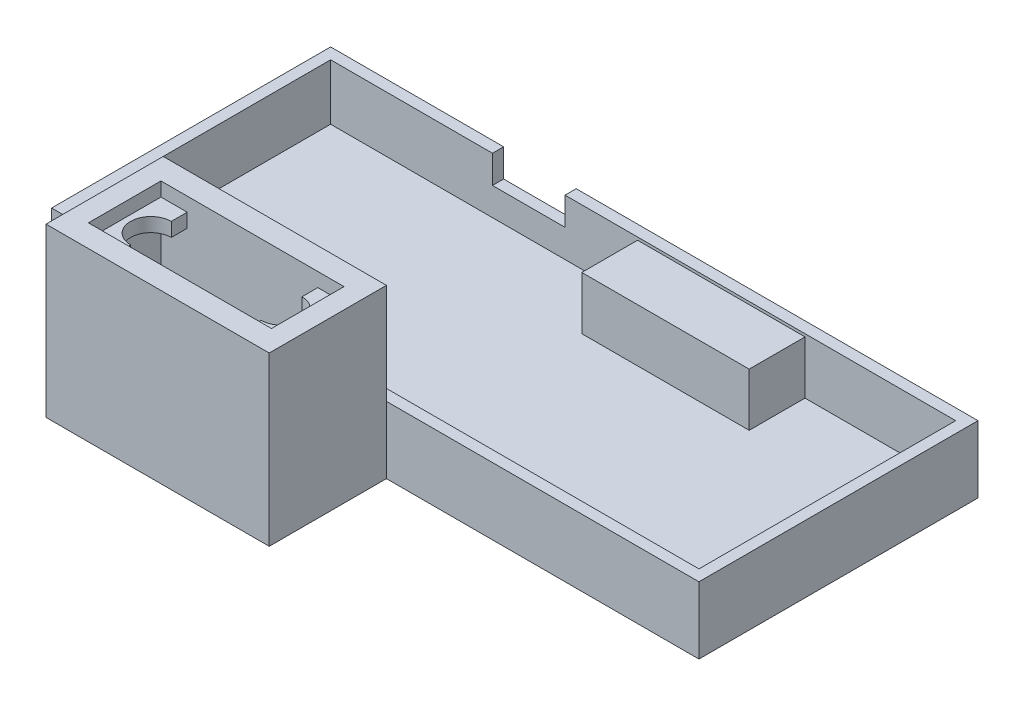
SolidWorks part; units mm, degrees
ref_plane "Front Plane" through (0, 0, 0) normal (0, 0, 1) x (1, 0, 0)
ref_plane "Top Plane" through (0, 0, 0) normal (0, 1, 0) x (1, 0, 0)
ref_plane "Right Plane" through (0, 0, 0) normal (1, 0, 0) x (0, 0, -1)
sketch "Sketch1" plane through (0, 0, 0) normal (0, 1, 0) x (1, 0, 0)
  line L1 (0, 0) -> (116, 0)
  line L2 (0, 0) -> (0, 50)
  line L3 (0, 50) -> (116, 50)
  line L4 (116, 0) -> (116, 50)
  dimension "D1" = 50
  dimension "D2" = 116
extrude "Boss-Extrude1" add sketch "Sketch1" along normal blind 2
sketch "Sketch2" plane through (0, 2, 0) normal (0, 1, 0) x (1, 0, 0)
  line L1 (0, 50) -> (116, 50)
  line L2 (0, 50) -> (0, 0)
  line L3 (0, 0) -> (116, 0)
  line L4 (116, 50) -> (116, 0)
  line L5 (2, 48) -> (114, 48)
  line L6 (2, 48) -> (2, 2)
  line L7 (2, 2) -> (114, 2)
  line L8 (114, 48) -> (114, 2)
  dimension "D1" = 2
  dimension "D2" = 2
  dimension "D3" = 2
  dimension "D4" = 2
extrude "Boss-Extrude3" add sketch "Sketch2" along normal blind 10
sketch "Sketch4" plane through (0, 2, 0) normal (0, 1, 0) x (1, 0, 0)
  line L0 (114, 48) -> (2, 48) construction
  line L1 (57, 48) -> (87, 48)
  line L2 (57, 48) -> (57, 38)
  line L3 (57, 38) -> (87, 38)
  line L4 (87, 48) -> (87, 38)
  dimension "D1" = 30
  dimension "D2" = 55
  dimension "D3" = 10
sketch "Sketch5" plane through (0, 0, -50) normal (0, 0, -1) x (-1, 0, 0)
  line L0 (-116, 12) -> (0, 12) construction
  line L1 (-31, 7) -> (-44, 7)
  line L2 (-31, 7) -> (-31, 12)
  line L3 (-31, 12) -> (-44, 12)
  line L4 (-44, 7) -> (-44, 12)
  dimension "D1" = 44
  dimension "D2" = 31
  dimension "D3" = 5
extrude "Cut-Extrude2" cut sketch "Sketch5" against normal blind 9.5
extrude "Boss-Extrude5" add sketch "Sketch4" along normal blind 9.5
sketch "Sketch6" plane through (0, 0, 0) normal (0, -1, 0) x (1, 0, 0)
  line L0 (0, 0) -> (116, 0) construction
  line L1 (20, 0) -> (60, 0)
  line L2 (20, 0) -> (20, 21)
  line L3 (20, 21) -> (60, 21)
  line L4 (60, 0) -> (60, 21)
  line L6 (28.3, 4) -> (51.7, 4)
  line L7 (28.3, 4) -> (28.3, 17)
  line L8 (28.3, 17) -> (51.7, 17)
  line L9 (51.7, 4) -> (51.7, 17)
  dimension "D1" = 21
  dimension "D2" = 40
  dimension "D3" = 13
  dimension "D4" = 23.4
  dimension "D5" = 4
  dimension "D6" = 8.3
  dimension "D7" = 20
extrude "Boss-Extrude6" add sketch "Sketch6" against normal blind 30
sketch "Sketch7" plane through (0, 30, 0) normal (0, 1, 0) x (1, 0, 0)
  line L0 (40, -23.6797) -> (40, -1.425) construction
  line L1 (51.7, -17) -> (56.4, -17)
  line L2 (51.7, -17) -> (51.7, -4)
  line L3 (51.7, -4) -> (56.4, -4)
  line L4 (56.4, -17) -> (56.4, -4)
  line L8 (23.6, -17) -> (23.6, -4)
  line L9 (28.3, -4) -> (23.6, -4)
  line L10 (28.3, -17) -> (28.3, -4)
  line L11 (28.3, -17) -> (23.6, -17)
  circle A0 centre (54.1, -10.5) radius 1.25
  circle A1 centre (25.9, -10.5) radius 1.25
  dimension "D2" = 2.3
  dimension "D3" = 2.5
  dimension "D1" = 4.7
  dimension "D4" = 6.5
  dimension "D5" = 11.7
extrude "Cut-Extrude3" cut sketch "Sketch7" against normal blind 2.5
sketch "Sketch8" plane through (0, 30, 0) normal (0, 1, 0) x (1, 0, 0)
  circle A0 centre (54.1, -10.5) radius 1.25
  circle A1 centre (25.9, -10.5) radius 1.25
extrude "Cut-Extrude4" cut sketch "Sketch8" against normal through all both and the other way through all
sketch "Sketch9" plane through (0, 27.5, 0) normal (0, 1, 0) x (1, 0, 0)
  line L0 (51.7, -4) -> (51.7, -17) construction
  line L1 (51.7, -13.1262) -> (51.7, -7.8738)
  arc A0 (51.7, -13.1262) -> (51.7, -7.8738) centre (52.5802, -10.5) ccw
  circle A1 centre (54.1, -10.5) radius 1.25 construction
  point P3 (54.1, -10.5)
extrude "Cut-Extrude5" cut sketch "Sketch9" against normal through all both and the other way through all
sketch "Sketch10" plane through (0, 0, 0) normal (0, -1, 0) x (1, 0, 0)
  line L0 (51.7, 17) -> (28.3, 17) construction
  line L1 (23.6, 17) -> (56.4, 17)
  line L2 (23.6, 17) -> (23.6, 4)
  line L3 (23.6, 4) -> (56.4, 4)
  line L4 (56.4, 17) -> (56.4, 4)
  line L5 (28.3, 4) -> (51.7, 4) construction
  dimension "D1" = 4.7
  dimension "D2" = 4.7
extrude "Cut-Extrude6" cut sketch "Sketch10" against normal blind 25
sketch "Sketch11" plane through (0, 27.5, 0) normal (0, 1, 0) x (1, 0, 0)
  line L0 (28.3, -17) -> (28.3, -4) construction
  line L1 (40, -18.2693) -> (40, -2.7988) construction
  line L3 (51.7, -14.15) -> (51.7, -6.85)
  line L4 (28.3, -14.15) -> (28.3, -6.85)
  arc A0 (28.3, -14.15) -> (28.3, -6.85) centre (28.3, -10.5) cw
  circle A1 centre (25.9, -10.5) radius 1.25 construction
  arc A2 (51.7, -14.15) -> (51.7, -6.85) centre (51.7, -10.5) ccw
  point P3 (25.9, -10.5)
  point P16 (54.1, -10.5)
  dimension "D1" = 11.7
extrude "Cut-Extrude7" cut sketch "Sketch11" against normal through all both and the other way through all
sketch "Sketch12" plane through (20, 0, 0) normal (-1, 0, 0) x (0, 0, 1)
  line L0 (21, 0) -> (0, 0) construction
  line L1 (4, 0) -> (17, 0)
  line L2 (4, 0) -> (4, 3.5)
  line L4 (17, 0) -> (17, 3.5)
  line L5 (0, 30) -> (0, 12) construction
  line L6 (21, 30) -> (21, 0) construction
  arc A0 (4, 3.5) -> (17, 3.5) centre (10.5, 3.5) cw
  dimension "D1" = 4
  dimension "D2" = 4
extrude "Cut-Extrude8" cut sketch "Sketch12" against normal blind 10
